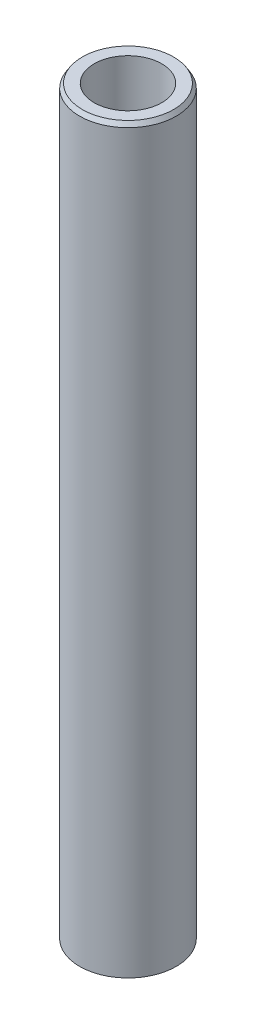
SolidWorks part; units mm, degrees
ref_plane "Front Plane" through (0, 0, 0) normal (0, 0, 1) x (1, 0, 0)
ref_plane "Top Plane" through (0, 0, 0) normal (0, 1, 0) x (1, 0, 0)
ref_plane "Right Plane" through (0, 0, 0) normal (1, 0, 0) x (0, 0, -1)
sketch "Sketch1" plane through (0, 0, 0) normal (0, 1, 0) x (1, 0, 0)
  circle A0 centre (0, 0) radius 25
  dimension "SHAFT_OD" = 50
extrude "Boss-Extrude1" add sketch "Sketch1" along normal blind 384.5526
sketch "Sketch2" plane through (0, 0, 0) normal (0, 1, 0) x (1, 0, 0)
  circle A0 centre (0, 0) radius 17.4736
  dimension "BORE_D" = 34.9472
extrude "Cut-Extrude1" cut sketch "Sketch2" along normal through all
chamfer "Chamfer1" distance 2.2475 angle 32.119 2 edges at (0, 384.5526, 25) (0, 0, 25) first distance on face at (0, 384.5526, 25) first distance on face at (0, 0, 17.4736)
